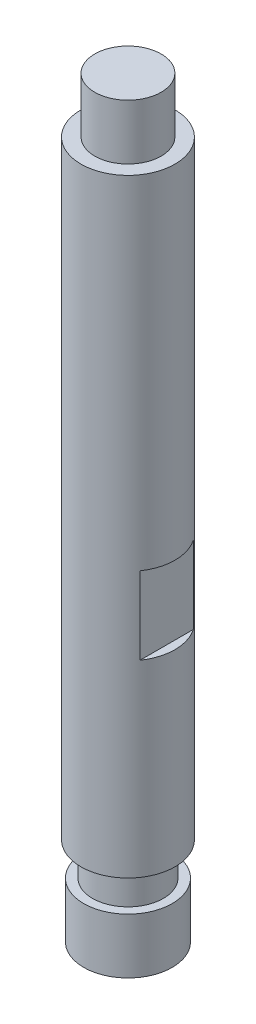
SolidWorks part; units mm, degrees
material "Alloy Steel"
ref_plane "Front Plane" through (0, 0, 0) normal (0, 0, 1) x (1, 0, 0)
ref_plane "Top Plane" through (0, 0, 0) normal (0, 1, 0) x (1, 0, 0)
ref_plane "Right Plane" through (0, 0, 0) normal (1, 0, 0) x (0, 0, -1)
sketch "Sketch1" plane through (0, 0, 0) normal (0, 1, 0) x (1, 0, 0)
  circle A0 centre (0, 0) radius 4.25
extrude "Boss-Extrude1" add sketch "Sketch1" along normal blind 55
ref_plane "Plane1" through (0, 55, 0) normal (0, 1, 0) x (1, 0, 0)
sketch "Sketch4" plane through (0, 55, 0) normal (0, 1, 0) x (1, 0, 0)
  circle A0 centre (0, 0) radius 3
extrude "Boss-Extrude3" add sketch "Sketch4" along normal blind 5
cosmetic thread "Cosmetic Thread1" parameters "D2"=4.891
sketch "Sketch5" plane through (0, 0, 0) normal (0, 0, 1) x (1, 0, 0)
  line L0 (4.25, 0) -> (4.25, 55) construction
  line L1 (-4.25, 55) -> (-4.25, 0) construction
  line L2 (-4.25, 17) -> (-4.25, 24)
  line L24 (3.5, 24) -> (4.25, 24)
  line L26 (3.5, 17) -> (4.25, 17)
  line L27 (4.25, 17) -> (4.25, 24)
  line L28 (-3.5, 17) -> (-4.25, 17)
  line L30 (-3.5, 24) -> (-4.25, 24)
  line L32 (-3.5, 24) -> (-3.5, 17)
  line L33 (3.5, 24) -> (3.5, 17)
  point P5 (-3.4841, 17.2309)
  dimension "D1" = 7
  dimension "D2" = 17
  dimension "D3" = 0.75
extrude "Cut-Extrude2" cut sketch "Sketch5" against normal blind 10 and the other way blind 10
sketch "Sketch3" plane through (0, 0, 0) normal (0, 1, 0) x (1, 0, 0)
  circle A0 centre (0, 0) radius 4
extrude "Boss-Extrude2" add sketch "Sketch3" against normal blind 8
cosmetic thread "Cosmetic Thread2" parameters "D1"=5, "D2"=6.619
sketch "Sketch6" plane through (0, 0, 0) normal (1, 0, 0) x (0, 0, -1)
  line L11 (4, 0) -> (3.2, 0)
  line L12 (4, 0) -> (4, -3)
  line L13 (4, -3) -> (3.2, -3)
  line L14 (3.2, 0) -> (3.2, -3)
ref_axis "Axis1" through (0, 55, 0) along (0, -1, 0)
revolve "Cut-Revolve1" cut sketch "Sketch6" angle 360 about axis through (0, 55, 0) along (0, -1, 0)
